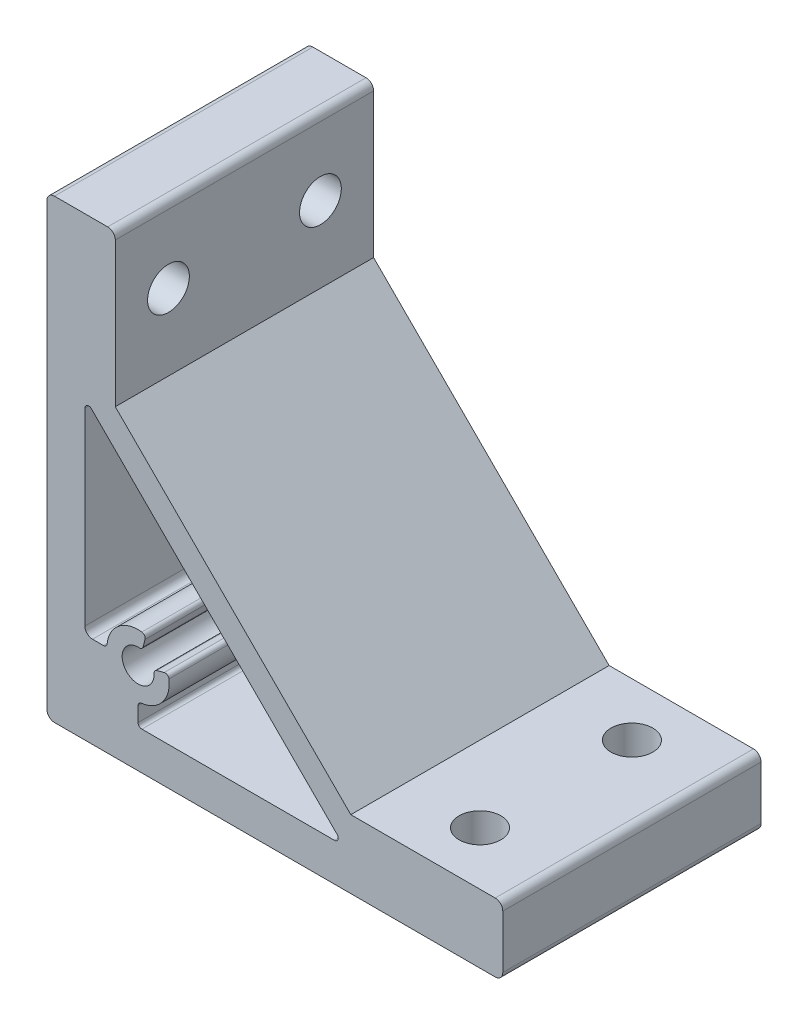
SolidWorks part; units mm, degrees
ref_plane "前视基准面" through (0, 0, 0) normal (0, 0, 1) x (1, 0, 0)
ref_plane "上视基准面" through (0, 0, 0) normal (0, 1, 0) x (1, 0, 0)
ref_plane "右视基准面" through (0, 0, 0) normal (1, 0, 0) x (0, 0, -1)
sketch "草图1" [suppressed] plane through (0, 0, 0) normal (0, 0, 1) x (1, 0, 0)
  line L12 (3, 3) -> (3, 19)
  line L13 (2, 20) -> (1, 20)
  line L14 (0, 19) -> (0, 1)
  line L15 (1, 0) -> (19, 0)
  line L16 (20, 1) -> (20, 2)
  line L17 (19, 3) -> (3, 3)
  arc A10 (3, 19) -> (2, 20) centre (2, 19) ccw
  arc A11 (1, 20) -> (0, 19) centre (1, 19) ccw
  arc A12 (0, 1) -> (1, 0) centre (1, 1) ccw
  arc A13 (19, 0) -> (20, 1) centre (19, 1) ccw
  arc A14 (20, 2) -> (19, 3) centre (19, 2) ccw
extrude "凸台-拉伸1" [suppressed] add sketch "草图1" against normal blind 14
sketch "草图2" [suppressed] plane through (0, 3, 0) normal (0, 1, 0) x (1, 0, 0)
  line L0 (19, 14) -> (3, 14) construction
  line L1 (0, 14) -> (0, 0) construction
  circle A0 centre (14, 7) radius 2.75
  dimension "D1" = 5.5
  dimension "D2" = 7
  dimension "D3" = 14
extrude "切除-拉伸1" [suppressed] cut sketch "草图2" against normal through all
sketch "草图3" [suppressed] plane through (3, 0, 0) normal (1, 0, 0) x (0, 0, -1)
  line L0 (0, 3) -> (0, 19) construction
  line L1 (14, 0) -> (0, 0) construction
  circle A0 centre (7, 14) radius 2.75
  dimension "D1" = 7
  dimension "D2" = 5.5
  dimension "D3" = 14
extrude "切除-拉伸2" [suppressed] cut sketch "草图3" against normal through all
sketch "草图4" [suppressed] plane through (0, 0, 0) normal (0, 0, 1) x (1, 0, 0)
  line L12 (3, 3) -> (3, 19)
  line L13 (2, 20) -> (1, 20)
  line L14 (0, 19) -> (0, 1)
  line L15 (1, 0) -> (19, 0)
  line L16 (20, 1) -> (20, 2)
  line L17 (19, 3) -> (3, 3)
  arc A10 (3, 19) -> (2, 20) centre (2, 19) ccw
  arc A11 (1, 20) -> (0, 19) centre (1, 19) ccw
  arc A12 (0, 1) -> (1, 0) centre (1, 1) ccw
  arc A13 (19, 0) -> (20, 1) centre (19, 1) ccw
  arc A14 (20, 2) -> (19, 3) centre (19, 2) ccw
extrude "凸台-拉伸2" [suppressed] add sketch "草图4" against normal blind 34
sketch "草图5" [suppressed] plane through (0, 3, 0) normal (0, 1, 0) x (1, 0, 0)
  line L0 (20, 17) -> (-10.7961, 17) construction
  line L1 (20, 34) -> (20, 0) construction
  line L2 (0, 34) -> (0, 0) construction
  circle A0 centre (14, 27) radius 2.75
  circle A1 centre (14, 7) radius 2.75
  dimension "D1" = 5.5
  dimension "D2" = 20
  dimension "D3" = 14
extrude "切除-拉伸3" [suppressed] cut sketch "草图5" against normal through all
sketch "草图6" [suppressed] plane through (3, 0, 0) normal (1, 0, 0) x (0, 0, -1)
  line L0 (17, 20) -> (17, -1.671) construction
  line L1 (34, 20) -> (0, 20) construction
  line L2 (34, 0) -> (0, 0) construction
  circle A0 centre (7, 14) radius 2.75
  circle A1 centre (27, 14) radius 2.75
  dimension "D1" = 5.5
  dimension "D2" = 20
  dimension "D3" = 14
extrude "切除-拉伸4" [suppressed] cut sketch "草图6" against normal through all
sketch "草图7" [suppressed] plane through (0, 0, 0) normal (0, 0, 1) x (1, 0, 0)
  line L12 (3, 3) -> (3, 19)
  line L13 (2, 20) -> (1, 20)
  line L14 (0, 19) -> (0, 1)
  line L15 (1, 0) -> (19, 0)
  line L16 (20, 1) -> (20, 2)
  line L17 (19, 3) -> (3, 3)
  arc A10 (3, 19) -> (2, 20) centre (2, 19) ccw
  arc A11 (1, 20) -> (0, 19) centre (1, 19) ccw
  arc A12 (0, 1) -> (1, 0) centre (1, 1) ccw
  arc A13 (19, 0) -> (20, 1) centre (19, 1) ccw
  arc A14 (20, 2) -> (19, 3) centre (19, 2) ccw
extrude "凸台-拉伸3" [suppressed] add sketch "草图7" against normal blind 54
sketch "草图8" [suppressed] plane through (0, 3, 0) normal (0, 1, 0) x (1, 0, 0)
  line L0 (20, 27) -> (-6.5003, 27) construction
  line L1 (20, 54) -> (20, 0) construction
  line L2 (0, 54) -> (0, 0) construction
  circle A0 centre (14, 47) radius 2.75
  circle A1 centre (14, 27) radius 2.75
  circle A2 centre (14, 7) radius 2.75
  dimension "D1" = 5.5
  dimension "D2" = 20
  dimension "D3" = 14
extrude "切除-拉伸5" [suppressed] cut sketch "草图8" against normal through all
sketch "草图9" [suppressed] plane through (3, 0, 0) normal (1, 0, 0) x (0, 0, -1)
  line L0 (27, 20) -> (27, 28.1098) construction
  line L1 (54, 20) -> (0, 20) construction
  line L2 (54, 0) -> (0, 0) construction
  circle A0 centre (7, 14) radius 2.75
  circle A1 centre (27, 14) radius 2.75
  circle A2 centre (47, 14) radius 2.75
  dimension "D1" = 5.5
  dimension "D2" = 20
  dimension "D3" = 14
extrude "切除-拉伸6" [suppressed] cut sketch "草图9" against normal through all
sketch "草图10" [suppressed] plane through (0, 0, 0) normal (0, 0, 1) x (1, 0, 0)
  line L20 (7.8119, 14.1881) -> (5, 17)
  line L21 (5, 17) -> (5, 34)
  line L22 (4, 35) -> (1, 35)
  line L23 (0, 34) -> (0, 1)
  line L24 (1, 0) -> (34, 0)
  line L25 (35, 1) -> (35, 4)
  line L26 (34, 5) -> (17, 5)
  line L27 (17, 5) -> (14.1881, 7.8119)
  line L28 (15.4436, 12.9222) -> (14.4646, 12.6602)
  line L29 (12.6602, 14.4646) -> (12.9222, 15.4436)
  arc A28 (5, 34) -> (4, 35) centre (4, 34) ccw
  arc A29 (1, 35) -> (0, 34) centre (1, 34) ccw
  arc A30 (0, 1) -> (1, 0) centre (1, 1) ccw
  arc A31 (34, 0) -> (35, 1) centre (34, 1) ccw
  arc A32 (35, 4) -> (34, 5) centre (34, 4) ccw
  arc A33 (14.265, 8.582) -> (14.1881, 7.8119) centre (14.5416, 8.1655) ccw
  arc A34 (14.265, 8.582) -> (16.069, 12.501) centre (11.9998, 11.9994) ccw
  arc A35 (16.069, 12.501) -> (15.4436, 12.9222) centre (15.5728, 12.4392) ccw
  arc A36 (14.4646, 12.6602) -> (14.095, 12.143) centre (14.5938, 12.1772) ccw
  arc A37 (12.143, 14.095) -> (14.095, 12.143) centre (11.9999, 11.9999) ccw
  arc A38 (12.143, 14.095) -> (12.6602, 14.4646) centre (12.1772, 14.5938) ccw
  arc A39 (12.9222, 15.4436) -> (12.501, 16.069) centre (12.4392, 15.5728) ccw
  arc A40 (12.501, 16.069) -> (8.582, 14.265) centre (11.9994, 11.9998) ccw
  arc A41 (7.8119, 14.1881) -> (8.582, 14.265) centre (8.1655, 14.5416) ccw
extrude "凸台-拉伸4" [suppressed] add sketch "草图10" against normal blind 14
sketch "草图11" [suppressed] plane through (0, 5, 0) normal (0, 1, 0) x (1, 0, 0)
  line L0 (34, 14) -> (17, 14) construction
  line L1 (0, 14) -> (0, 0) construction
  circle A0 centre (26, 7) radius 2.75
  dimension "D1" = 7
  dimension "D2" = 5.5
  dimension "D3" = 26
extrude "切除-拉伸7" [suppressed] cut sketch "草图11" against normal through all
sketch "草图12" [suppressed] plane through (5, 0, 0) normal (1, 0, 0) x (0, 0, -1)
  line L0 (0, 17) -> (0, 34) construction
  line L1 (14, 0) -> (0, 0) construction
  circle A0 centre (7, 26) radius 2.75
  dimension "D1" = 5.5
  dimension "D2" = 7
  dimension "D3" = 26
extrude "切除-拉伸8" [suppressed] cut sketch "草图12" against normal through all
sketch "草图13" [suppressed] plane through (0, 0, 0) normal (0, 0, 1) x (1, 0, 0)
  line L20 (7.8119, 14.1881) -> (5, 17)
  line L21 (5, 17) -> (5, 34)
  line L22 (4, 35) -> (1, 35)
  line L23 (0, 34) -> (0, 1)
  line L24 (1, 0) -> (34, 0)
  line L25 (35, 1) -> (35, 4)
  line L26 (34, 5) -> (17, 5)
  line L27 (17, 5) -> (14.1881, 7.8119)
  line L28 (15.4436, 12.9222) -> (14.4646, 12.6602)
  line L29 (12.6602, 14.4646) -> (12.9222, 15.4436)
  arc A28 (5, 34) -> (4, 35) centre (4, 34) ccw
  arc A29 (1, 35) -> (0, 34) centre (1, 34) ccw
  arc A30 (0, 1) -> (1, 0) centre (1, 1) ccw
  arc A31 (34, 0) -> (35, 1) centre (34, 1) ccw
  arc A32 (35, 4) -> (34, 5) centre (34, 4) ccw
  arc A33 (14.265, 8.582) -> (14.1881, 7.8119) centre (14.5416, 8.1655) ccw
  arc A34 (14.265, 8.582) -> (16.069, 12.501) centre (11.9998, 11.9994) ccw
  arc A35 (16.069, 12.501) -> (15.4436, 12.9222) centre (15.5728, 12.4392) ccw
  arc A36 (14.4646, 12.6602) -> (14.095, 12.143) centre (14.5938, 12.1772) ccw
  arc A37 (12.143, 14.095) -> (14.095, 12.143) centre (11.9999, 11.9999) ccw
  arc A38 (12.143, 14.095) -> (12.6602, 14.4646) centre (12.1772, 14.5938) ccw
  arc A39 (12.9222, 15.4436) -> (12.501, 16.069) centre (12.4392, 15.5728) ccw
  arc A40 (12.501, 16.069) -> (8.582, 14.265) centre (11.9994, 11.9998) ccw
  arc A41 (7.8119, 14.1881) -> (8.582, 14.265) centre (8.1655, 14.5416) ccw
extrude "凸台-拉伸5" [suppressed] add sketch "草图13" against normal blind 34
sketch "草图14" [suppressed] plane through (0, 5, 0) normal (0, 1, 0) x (1, 0, 0)
  line L0 (35, 17) -> (-9.0369, 17) construction
  line L1 (35, 34) -> (35, 0) construction
  line L2 (0, 34) -> (0, 0) construction
  circle A0 centre (26, 27) radius 2.75
  circle A1 centre (26, 7) radius 2.75
  dimension "D1" = 5.5
  dimension "D2" = 20
  dimension "D3" = 26
extrude "切除-拉伸9" [suppressed] cut sketch "草图14" against normal through all
sketch "草图15" [suppressed] plane through (5, 0, 0) normal (1, 0, 0) x (0, 0, -1)
  line L0 (17, 35) -> (17, -2.0911) construction
  line L1 (34, 35) -> (0, 35) construction
  line L2 (34, 0) -> (0, 0) construction
  circle A0 centre (7, 26) radius 2.75
  circle A1 centre (27, 26) radius 2.75
  dimension "D1" = 5.5
  dimension "D2" = 20
  dimension "D3" = 26
extrude "切除-拉伸10" [suppressed] cut sketch "草图15" against normal through all
sketch "草图16" [suppressed] plane through (0, 0, 0) normal (0, 0, 1) x (1, 0, 0)
  line L20 (7.8119, 14.1881) -> (5, 17)
  line L21 (5, 17) -> (5, 34)
  line L22 (4, 35) -> (1, 35)
  line L23 (0, 34) -> (0, 1)
  line L24 (1, 0) -> (34, 0)
  line L25 (35, 1) -> (35, 4)
  line L26 (34, 5) -> (17, 5)
  line L27 (17, 5) -> (14.1881, 7.8119)
  line L28 (15.4436, 12.9222) -> (14.4646, 12.6602)
  line L29 (12.6602, 14.4646) -> (12.9222, 15.4436)
  arc A28 (5, 34) -> (4, 35) centre (4, 34) ccw
  arc A29 (1, 35) -> (0, 34) centre (1, 34) ccw
  arc A30 (0, 1) -> (1, 0) centre (1, 1) ccw
  arc A31 (34, 0) -> (35, 1) centre (34, 1) ccw
  arc A32 (35, 4) -> (34, 5) centre (34, 4) ccw
  arc A33 (14.265, 8.582) -> (14.1881, 7.8119) centre (14.5416, 8.1655) ccw
  arc A34 (14.265, 8.582) -> (16.069, 12.501) centre (11.9998, 11.9994) ccw
  arc A35 (16.069, 12.501) -> (15.4436, 12.9222) centre (15.5728, 12.4392) ccw
  arc A36 (14.4646, 12.6602) -> (14.095, 12.143) centre (14.5938, 12.1772) ccw
  arc A37 (12.143, 14.095) -> (14.095, 12.143) centre (11.9999, 11.9999) ccw
  arc A38 (12.143, 14.095) -> (12.6602, 14.4646) centre (12.1772, 14.5938) ccw
  arc A39 (12.9222, 15.4436) -> (12.501, 16.069) centre (12.4392, 15.5728) ccw
  arc A40 (12.501, 16.069) -> (8.582, 14.265) centre (11.9994, 11.9998) ccw
  arc A41 (7.8119, 14.1881) -> (8.582, 14.265) centre (8.1655, 14.5416) ccw
extrude "凸台-拉伸6" [suppressed] add sketch "草图16" against normal blind 54
sketch "草图17" [suppressed] plane through (0, 5, 0) normal (0, 1, 0) x (1, 0, 0)
  line L0 (35, 27) -> (46.9961, 27) construction
  line L1 (35, 54) -> (35, 0) construction
  line L2 (0, 54) -> (0, 0) construction
  circle A0 centre (26, 47) radius 2.75
  circle A1 centre (26, 27) radius 2.75
  circle A2 centre (26, 7) radius 2.75
  dimension "D1" = 5.5
  dimension "D2" = 20
  dimension "D3" = 26
extrude "切除-拉伸11" [suppressed] cut sketch "草图17" against normal through all
sketch "草图18" [suppressed] plane through (5, 0, 0) normal (1, 0, 0) x (0, 0, -1)
  line L0 (27, 35) -> (27, 41.3305) construction
  line L1 (54, 35) -> (0, 35) construction
  line L2 (54, 0) -> (0, 0) construction
  circle A0 centre (7, 26) radius 2.75
  circle A1 centre (27, 26) radius 2.75
  circle A2 centre (47, 26) radius 2.75
  dimension "D1" = 5.5
  dimension "D2" = 20
  dimension "D3" = 26
extrude "切除-拉伸12" [suppressed] cut sketch "草图18" against normal through all
sketch "草图19" [suppressed] plane through (0, 0, 0) normal (0, 0, 1) x (1, 0, 0)
  line L16 (-14.794, 9) -> (-54, 9)
  line L17 (-55, 8) -> (-55, 1)
  line L18 (-54, 0) -> (-1, 0)
  line L19 (0, 1) -> (0, 54)
  line L20 (-1, 55) -> (-8, 55)
  line L21 (-9, 54) -> (-9, 14.795)
  line L22 (-12.9219, 15.4435) -> (-12.6599, 14.4646)
  line L23 (-14.4641, 12.66) -> (-15.443, 12.923)
  arc A24 (-15.443, 12.923) -> (-16.069, 12.501) centre (-15.5727, 12.4401) ccw
  arc A25 (-16.069, 12.501) -> (-14.794, 9) centre (-11.9997, 12.0003) ccw
  arc A26 (-54, 9) -> (-55, 8) centre (-54, 8) ccw
  arc A27 (-55, 1) -> (-54, 0) centre (-54, 1) ccw
  arc A28 (-1, 0) -> (0, 1) centre (-1, 1) ccw
  arc A29 (0, 54) -> (-1, 55) centre (-1, 54) ccw
  arc A30 (-8, 55) -> (-9, 54) centre (-8, 54) ccw
  arc A31 (-9, 14.795) -> (-12.5, 16.069) centre (-11.9994, 11.9997) ccw
  arc A32 (-12.5, 16.069) -> (-12.9219, 15.4435) centre (-12.4389, 15.5728) ccw
  arc A33 (-12.6599, 14.4646) -> (-12.143, 14.095) centre (-12.1769, 14.5939) ccw
  arc A34 (-14.095, 12.143) -> (-12.143, 14.095) centre (-11.9999, 11.9999) ccw
  arc A35 (-14.095, 12.143) -> (-14.4641, 12.66) centre (-14.5938, 12.1772) ccw
extrude "凸台-拉伸7" [suppressed] add sketch "草图19" against normal blind 14
sketch "草图20" [suppressed] plane through (-9, 0, 0) normal (-1, 0, 0) x (0, 0, 1)
  line L0 (-14, 54) -> (-14, 14.795) construction
  line L1 (-14, 0) -> (0, 0) construction
  circle A0 centre (-7, 25) radius 2.75
  circle A1 centre (-7, 45) radius 2.75
  dimension "D1" = 5.5
  dimension "D2" = 7
  dimension "D3" = 25
  dimension "D4" = 45
extrude "切除-拉伸13" [suppressed] cut sketch "草图20" against normal through all
sketch "草图21" [suppressed] plane through (0, 9, 0) normal (0, 1, 0) x (1, 0, 0)
  line L0 (-14.794, 0) -> (-54, 0) construction
  line L1 (0, 14) -> (0, 0) construction
  circle A0 centre (-45, 7) radius 2.75
  circle A1 centre (-25, 7) radius 2.75
  dimension "D1" = 5.5
  dimension "D2" = 7
  dimension "D3" = 25
  dimension "D4" = 45
extrude "切除-拉伸14" [suppressed] cut sketch "草图21" against normal through all
sketch "草图22" [suppressed] plane through (0, 0, 0) normal (0, 0, 1) x (1, 0, 0)
  line L16 (-14.794, 9) -> (-54, 9)
  line L17 (-55, 8) -> (-55, 1)
  line L18 (-54, 0) -> (-1, 0)
  line L19 (0, 1) -> (0, 54)
  line L20 (-1, 55) -> (-8, 55)
  line L21 (-9, 54) -> (-9, 14.795)
  line L22 (-12.9219, 15.4435) -> (-12.6599, 14.4646)
  line L23 (-14.4641, 12.66) -> (-15.443, 12.923)
  arc A24 (-15.443, 12.923) -> (-16.069, 12.501) centre (-15.5727, 12.4401) ccw
  arc A25 (-16.069, 12.501) -> (-14.794, 9) centre (-11.9997, 12.0003) ccw
  arc A26 (-54, 9) -> (-55, 8) centre (-54, 8) ccw
  arc A27 (-55, 1) -> (-54, 0) centre (-54, 1) ccw
  arc A28 (-1, 0) -> (0, 1) centre (-1, 1) ccw
  arc A29 (0, 54) -> (-1, 55) centre (-1, 54) ccw
  arc A30 (-8, 55) -> (-9, 54) centre (-8, 54) ccw
  arc A31 (-9, 14.795) -> (-12.5, 16.069) centre (-11.9994, 11.9997) ccw
  arc A32 (-12.5, 16.069) -> (-12.9219, 15.4435) centre (-12.4389, 15.5728) ccw
  arc A33 (-12.6599, 14.4646) -> (-12.143, 14.095) centre (-12.1769, 14.5939) ccw
  arc A34 (-14.095, 12.143) -> (-12.143, 14.095) centre (-11.9999, 11.9999) ccw
  arc A35 (-14.095, 12.143) -> (-14.4641, 12.66) centre (-14.5938, 12.1772) ccw
extrude "凸台-拉伸8" [suppressed] add sketch "草图22" against normal blind 34
sketch "草图23" [suppressed] plane through (-9, 0, 0) normal (-1, 0, 0) x (0, 0, 1)
  line L0 (-17, 55) -> (-17, 18.2791) construction
  line L1 (-34, 55) -> (0, 55) construction
  line L2 (-34, 0) -> (0, 0) construction
  circle A0 centre (-27, 45) radius 2.75
  circle A1 centre (-7, 45) radius 2.75
  circle A2 centre (-27, 25) radius 2.75
  circle A3 centre (-7, 25) radius 2.75
  dimension "D1" = 5.5
  dimension "D2" = 20
  dimension "D3" = 25
  dimension "D4" = 45
extrude "切除-拉伸15" [suppressed] cut sketch "草图23" against normal through all
sketch "草图24" [suppressed] plane through (0, 9, 0) normal (0, 1, 0) x (1, 0, 0)
  line L0 (-55, 17) -> (-20.4322, 17) construction
  line L1 (-55, 34) -> (-55, 0) construction
  line L2 (0, 34) -> (0, 0) construction
  circle A0 centre (-45, 27) radius 2.75
  circle A1 centre (-25, 27) radius 2.75
  circle A2 centre (-45, 7) radius 2.75
  circle A3 centre (-25, 7) radius 2.75
  dimension "D1" = 5.5
  dimension "D2" = 20
  dimension "D3" = 25
  dimension "D4" = 45
extrude "切除-拉伸16" [suppressed] cut sketch "草图24" against normal through all
sketch "草图25" [suppressed] plane through (0, 0, 0) normal (0, 0, 1) x (1, 0, 0)
  line L16 (-14.794, 9) -> (-54, 9)
  line L17 (-55, 8) -> (-55, 1)
  line L18 (-54, 0) -> (-1, 0)
  line L19 (0, 1) -> (0, 54)
  line L20 (-1, 55) -> (-8, 55)
  line L21 (-9, 54) -> (-9, 14.795)
  line L22 (-12.9219, 15.4435) -> (-12.6599, 14.4646)
  line L23 (-14.4641, 12.66) -> (-15.443, 12.923)
  arc A24 (-15.443, 12.923) -> (-16.069, 12.501) centre (-15.5727, 12.4401) ccw
  arc A25 (-16.069, 12.501) -> (-14.794, 9) centre (-11.9997, 12.0003) ccw
  arc A26 (-54, 9) -> (-55, 8) centre (-54, 8) ccw
  arc A27 (-55, 1) -> (-54, 0) centre (-54, 1) ccw
  arc A28 (-1, 0) -> (0, 1) centre (-1, 1) ccw
  arc A29 (0, 54) -> (-1, 55) centre (-1, 54) ccw
  arc A30 (-8, 55) -> (-9, 54) centre (-8, 54) ccw
  arc A31 (-9, 14.795) -> (-12.5, 16.069) centre (-11.9994, 11.9997) ccw
  arc A32 (-12.5, 16.069) -> (-12.9219, 15.4435) centre (-12.4389, 15.5728) ccw
  arc A33 (-12.6599, 14.4646) -> (-12.143, 14.095) centre (-12.1769, 14.5939) ccw
  arc A34 (-14.095, 12.143) -> (-12.143, 14.095) centre (-11.9999, 11.9999) ccw
  arc A35 (-14.095, 12.143) -> (-14.4641, 12.66) centre (-14.5938, 12.1772) ccw
extrude "凸台-拉伸9" [suppressed] add sketch "草图25" against normal blind 54
sketch "草图26" [suppressed] plane through (-9, 0, 0) normal (-1, 0, 0) x (0, 0, 1)
  line L0 (-27, 55) -> (-27, 17.8329) construction
  line L1 (-54, 55) -> (0, 55) construction
  line L2 (-54, 0) -> (0, 0) construction
  circle A0 centre (-47, 45) radius 2.75
  circle A1 centre (-27, 45) radius 2.75
  circle A2 centre (-7, 45) radius 2.75
  circle A3 centre (-7, 25) radius 2.75
  circle A4 centre (-27, 25) radius 2.75
  circle A5 centre (-47, 25) radius 2.75
  dimension "D1" = 5.5
  dimension "D2" = 20
  dimension "D3" = 25
  dimension "D4" = 45
extrude "切除-拉伸17" [suppressed] cut sketch "草图26" against normal through all
sketch "草图27" [suppressed] plane through (0, 9, 0) normal (0, 1, 0) x (1, 0, 0)
  line L0 (-55, 27) -> (-66.2684, 27) construction
  line L1 (-55, 54) -> (-55, 0) construction
  line L2 (0, 54) -> (0, 0) construction
  circle A0 centre (-45, 47) radius 2.75
  circle A1 centre (-25, 47) radius 2.75
  circle A2 centre (-45, 27) radius 2.75
  circle A3 centre (-25, 27) radius 2.75
  circle A4 centre (-45, 7) radius 2.75
  circle A5 centre (-25, 7) radius 2.75
  dimension "D1" = 5.5
  dimension "D2" = 20
  dimension "D3" = 25
  dimension "D4" = 45
extrude "切除-拉伸18" [suppressed] cut sketch "草图27" against normal through all
sketch "草图28" [suppressed] plane through (0, 0, 0) normal (0, 0, 1) x (1, 0, 0)
  line L14 (9, 30) -> (9, 49)
  line L15 (8, 50) -> (1, 50)
  line L16 (0, 49) -> (0, 1)
  line L17 (1, 0) -> (49, 0)
  line L18 (50, 1) -> (50, 8)
  line L19 (49, 9) -> (30, 9)
  line L20 (30, 9) -> (9, 30)
  line L28 (5.5, 12) -> (7.428, 12)
  line L29 (5, 27.8439) -> (5, 12.5)
  line L30 (28.1965, 5.8535) -> (5.8536, 28.1974)
  line L31 (12.5, 5) -> (27.8429, 5)
  line L32 (12, 7.4269) -> (12, 5.5)
  line L33 (14.4641, 12.6598) -> (15.444, 12.923)
  line L34 (12.9231, 15.4435) -> (12.6612, 14.4646)
  arc A10 (9, 49) -> (8, 50) centre (8, 49) ccw
  arc A11 (1, 50) -> (0, 49) centre (1, 49) ccw
  arc A12 (0, 1) -> (1, 0) centre (1, 1) ccw
  arc A13 (49, 0) -> (50, 1) centre (49, 1) ccw
  arc A14 (50, 8) -> (49, 9) centre (49, 8) ccw
  arc A36 (7.428, 12) -> (7.925, 12.445) centre (7.428, 12.5) ccw
  arc A37 (5, 12.5) -> (5.5, 12) centre (5.5, 12.5) ccw
  arc A38 (5.8536, 28.1974) -> (5, 27.8439) centre (5.5, 27.8439) ccw
  arc A39 (27.8429, 5) -> (28.1965, 5.8535) centre (27.8429, 5.5) ccw
  arc A40 (12, 5.5) -> (12.5, 5) centre (12.5, 5.5) ccw
  arc A41 (12.446, 7.924) -> (12, 7.4269) centre (12.5, 7.4269) ccw
  arc A42 (12.446, 7.924) -> (16.07, 12.501) centre (12.0008, 11.9998) ccw
  arc A43 (16.07, 12.501) -> (15.444, 12.923) centre (15.5737, 12.4401) ccw
  arc A44 (14.4641, 12.6598) -> (14.095, 12.143) centre (14.5939, 12.1769) ccw
  arc A45 (12.144, 14.095) -> (14.095, 12.143) centre (11.9999, 12) ccw
  arc A46 (12.144, 14.095) -> (12.6612, 14.4646) centre (12.1782, 14.5938) ccw
  arc A47 (12.9231, 15.4435) -> (12.501, 16.069) centre (12.4401, 15.5727) ccw
  arc A48 (12.501, 16.069) -> (7.925, 12.445) centre (12.0007, 11.9996) ccw
extrude "凸台-拉伸10" [suppressed] add sketch "草图28" along normal blind 14
sketch "草图29" [suppressed] plane through (9, 0, 0) normal (1, 0, 0) x (0, 0, -1)
  line L0 (-14, 30) -> (-14, 49) construction
  line L1 (-14, 0) -> (0, 0) construction
  circle A0 centre (-7, 40) radius 2.75
  dimension "D1" = 7
  dimension "D2" = 5.5
  dimension "D3" = 40
extrude "切除-拉伸19" [suppressed] cut sketch "草图29" against normal through all
sketch "草图30" [suppressed] plane through (0, 9, 0) normal (0, 1, 0) x (1, 0, 0)
  line L0 (49, 0) -> (30, 0) construction
  line L1 (0, -14) -> (0, 0) construction
  circle A0 centre (40, -7) radius 2.75
  dimension "D1" = 5.5
  dimension "D2" = 7
  dimension "D3" = 40
extrude "切除-拉伸20" [suppressed] cut sketch "草图30" against normal through all
sketch "草图31" [suppressed] plane through (0, 0, 0) normal (0, 0, 1) x (1, 0, 0)
  line L14 (9, 30) -> (9, 49)
  line L15 (8, 50) -> (1, 50)
  line L16 (0, 49) -> (0, 1)
  line L17 (1, 0) -> (49, 0)
  line L18 (50, 1) -> (50, 8)
  line L19 (49, 9) -> (30, 9)
  line L20 (30, 9) -> (9, 30)
  line L28 (5.5, 12) -> (7.428, 12)
  line L29 (5, 27.8439) -> (5, 12.5)
  line L30 (28.1965, 5.8535) -> (5.8536, 28.1974)
  line L31 (12.5, 5) -> (27.8429, 5)
  line L32 (12, 7.4269) -> (12, 5.5)
  line L33 (14.4641, 12.6598) -> (15.444, 12.923)
  line L34 (12.9231, 15.4435) -> (12.6612, 14.4646)
  arc A10 (9, 49) -> (8, 50) centre (8, 49) ccw
  arc A11 (1, 50) -> (0, 49) centre (1, 49) ccw
  arc A12 (0, 1) -> (1, 0) centre (1, 1) ccw
  arc A13 (49, 0) -> (50, 1) centre (49, 1) ccw
  arc A14 (50, 8) -> (49, 9) centre (49, 8) ccw
  arc A36 (7.428, 12) -> (7.925, 12.445) centre (7.428, 12.5) ccw
  arc A37 (5, 12.5) -> (5.5, 12) centre (5.5, 12.5) ccw
  arc A38 (5.8536, 28.1974) -> (5, 27.8439) centre (5.5, 27.8439) ccw
  arc A39 (27.8429, 5) -> (28.1965, 5.8535) centre (27.8429, 5.5) ccw
  arc A40 (12, 5.5) -> (12.5, 5) centre (12.5, 5.5) ccw
  arc A41 (12.446, 7.924) -> (12, 7.4269) centre (12.5, 7.4269) ccw
  arc A42 (12.446, 7.924) -> (16.07, 12.501) centre (12.0008, 11.9998) ccw
  arc A43 (16.07, 12.501) -> (15.444, 12.923) centre (15.5737, 12.4401) ccw
  arc A44 (14.4641, 12.6598) -> (14.095, 12.143) centre (14.5939, 12.1769) ccw
  arc A45 (12.144, 14.095) -> (14.095, 12.143) centre (11.9999, 12) ccw
  arc A46 (12.144, 14.095) -> (12.6612, 14.4646) centre (12.1782, 14.5938) ccw
  arc A47 (12.9231, 15.4435) -> (12.501, 16.069) centre (12.4401, 15.5727) ccw
  arc A48 (12.501, 16.069) -> (7.925, 12.445) centre (12.0007, 11.9996) ccw
extrude "凸台-拉伸11" [suppressed] add sketch "草图31" against normal blind 34
sketch "草图32" [suppressed] plane through (0, 9, 0) normal (0, 1, 0) x (1, 0, 0)
  line L0 (50, 17) -> (60.62, 17) construction
  line L1 (50, 34) -> (50, 0) construction
  line L2 (0, 34) -> (0, 0) construction
  circle A0 centre (40, 27) radius 2.75
  circle A1 centre (40, 7) radius 2.75
  dimension "D1" = 5.5
  dimension "D2" = 20
  dimension "D3" = 40
extrude "切除-拉伸21" [suppressed] cut sketch "草图32" against normal through all
sketch "草图33" [suppressed] plane through (9, 0, 0) normal (1, 0, 0) x (0, 0, -1)
  line L0 (17, 50) -> (17, 18.713) construction
  line L1 (34, 50) -> (0, 50) construction
  line L2 (34, 0) -> (0, 0) construction
  circle A0 centre (7, 40) radius 2.75
  circle A1 centre (27, 40) radius 2.75
  dimension "D1" = 5.5
  dimension "D2" = 20
  dimension "D3" = 40
extrude "切除-拉伸22" [suppressed] cut sketch "草图33" against normal through all
sketch "草图34" [suppressed] plane through (0, 0, 0) normal (0, 0, 1) x (1, 0, 0)
  line L14 (9, 30) -> (9, 49)
  line L15 (8, 50) -> (1, 50)
  line L16 (0, 49) -> (0, 1)
  line L17 (1, 0) -> (49, 0)
  line L18 (50, 1) -> (50, 8)
  line L19 (49, 9) -> (30, 9)
  line L20 (30, 9) -> (9, 30)
  line L28 (5.5, 12) -> (7.428, 12)
  line L29 (5, 27.8439) -> (5, 12.5)
  line L30 (28.1965, 5.8535) -> (5.8536, 28.1974)
  line L31 (12.5, 5) -> (27.8429, 5)
  line L32 (12, 7.4269) -> (12, 5.5)
  line L33 (14.4641, 12.6598) -> (15.444, 12.923)
  line L34 (12.9231, 15.4435) -> (12.6612, 14.4646)
  arc A10 (9, 49) -> (8, 50) centre (8, 49) ccw
  arc A11 (1, 50) -> (0, 49) centre (1, 49) ccw
  arc A12 (0, 1) -> (1, 0) centre (1, 1) ccw
  arc A13 (49, 0) -> (50, 1) centre (49, 1) ccw
  arc A14 (50, 8) -> (49, 9) centre (49, 8) ccw
  arc A36 (7.428, 12) -> (7.925, 12.445) centre (7.428, 12.5) ccw
  arc A37 (5, 12.5) -> (5.5, 12) centre (5.5, 12.5) ccw
  arc A38 (5.8536, 28.1974) -> (5, 27.8439) centre (5.5, 27.8439) ccw
  arc A39 (27.8429, 5) -> (28.1965, 5.8535) centre (27.8429, 5.5) ccw
  arc A40 (12, 5.5) -> (12.5, 5) centre (12.5, 5.5) ccw
  arc A41 (12.446, 7.924) -> (12, 7.4269) centre (12.5, 7.4269) ccw
  arc A42 (12.446, 7.924) -> (16.07, 12.501) centre (12.0008, 11.9998) ccw
  arc A43 (16.07, 12.501) -> (15.444, 12.923) centre (15.5737, 12.4401) ccw
  arc A44 (14.4641, 12.6598) -> (14.095, 12.143) centre (14.5939, 12.1769) ccw
  arc A45 (12.144, 14.095) -> (14.095, 12.143) centre (11.9999, 12) ccw
  arc A46 (12.144, 14.095) -> (12.6612, 14.4646) centre (12.1782, 14.5938) ccw
  arc A47 (12.9231, 15.4435) -> (12.501, 16.069) centre (12.4401, 15.5727) ccw
  arc A48 (12.501, 16.069) -> (7.925, 12.445) centre (12.0007, 11.9996) ccw
extrude "凸台-拉伸12" [suppressed] add sketch "草图34" against normal blind 54
sketch "草图35" [suppressed] plane through (0, 9, 0) normal (0, 1, 0) x (1, 0, 0)
  line L0 (50, 27) -> (60.775, 27) construction
  line L1 (50, 54) -> (50, 0) construction
  line L2 (0, 54) -> (0, 0) construction
  circle A0 centre (40, 47) radius 2.75
  circle A1 centre (40, 27) radius 2.75
  circle A2 centre (40, 7) radius 2.75
  dimension "D1" = 5.5
  dimension "D2" = 20
  dimension "D3" = 40
extrude "切除-拉伸23" [suppressed] cut sketch "草图35" against normal through all
sketch "草图36" [suppressed] plane through (9, 0, 0) normal (1, 0, 0) x (0, 0, -1)
  line L0 (27, 50) -> (27, 56.3689) construction
  line L1 (54, 50) -> (0, 50) construction
  line L2 (54, 0) -> (0, 0) construction
  circle A0 centre (7, 40) radius 2.75
  circle A1 centre (27, 40) radius 2.75
  circle A2 centre (47, 40) radius 2.75
  dimension "D1" = 5.5
  dimension "D2" = 20
  dimension "D3" = 40
extrude "切除-拉伸24" [suppressed] cut sketch "草图36" against normal through all
sketch "草图37" [suppressed] plane through (0, 0, 0) normal (0, 0, 1) x (1, 0, 0)
  line L14 (40, 9) -> (9, 40)
  line L15 (9, 40) -> (9, 59)
  line L16 (8, 60) -> (1, 60)
  line L17 (0, 59) -> (0, 1)
  line L18 (1, 0) -> (59, 0)
  line L19 (60, 1) -> (60, 8)
  line L20 (59, 9) -> (40, 9)
  line L28 (6, 12) -> (7.428, 12)
  line L29 (5, 37.8429) -> (5, 13)
  line L30 (38.1964, 5.8536) -> (5.8536, 38.1964)
  line L31 (12.5, 5) -> (37.844, 5)
  line L32 (12, 7.4269) -> (12, 5.5)
  line L33 (14.4656, 12.6602) -> (15.4446, 12.9222)
  line L34 (12.9231, 15.4435) -> (12.6612, 14.4646)
  arc A10 (9, 59) -> (8, 60) centre (8, 59) ccw
  arc A11 (1, 60) -> (0, 59) centre (1, 59) ccw
  arc A12 (0, 1) -> (1, 0) centre (1, 1) ccw
  arc A13 (59, 0) -> (60, 1) centre (59, 1) ccw
  arc A14 (60, 8) -> (59, 9) centre (59, 8) ccw
  arc A36 (12.501, 16.069) -> (7.925, 12.445) centre (12.0007, 11.9996) ccw
  arc A37 (7.428, 12) -> (7.925, 12.445) centre (7.428, 12.5) ccw
  arc A38 (5, 13) -> (6, 12) centre (6, 13) ccw
  arc A39 (5.8536, 38.1964) -> (5, 37.8429) centre (5.5, 37.8429) ccw
  arc A40 (37.844, 5) -> (38.1964, 5.8536) centre (37.8429, 5.5) ccw
  arc A41 (12, 5.5) -> (12.5, 5) centre (12.5, 5.5) ccw
  arc A42 (12.446, 7.924) -> (12, 7.4269) centre (12.5, 7.4269) ccw
  arc A43 (12.446, 7.924) -> (16.07, 12.501) centre (12.0008, 11.9998) ccw
  arc A44 (16.07, 12.501) -> (15.4446, 12.9222) centre (15.5738, 12.4392) ccw
  arc A45 (14.4656, 12.6602) -> (14.096, 12.143) centre (14.5948, 12.1772) ccw
  arc A46 (12.144, 14.095) -> (14.096, 12.143) centre (12.0009, 11.9999) ccw
  arc A47 (12.144, 14.095) -> (12.6612, 14.4646) centre (12.1782, 14.5938) ccw
  arc A48 (12.9231, 15.4435) -> (12.501, 16.069) centre (12.4401, 15.5727) ccw
extrude "凸台-拉伸13" [suppressed] add sketch "草图37" against normal blind 14
sketch "草图38" [suppressed] plane through (0, 9, 0) normal (0, 1, 0) x (1, 0, 0)
  line L0 (59, 14) -> (40, 14) construction
  line L1 (0, 14) -> (0, 0) construction
  circle A0 centre (50, 7) radius 2.75
  dimension "D1" = 5.5
  dimension "D2" = 7
  dimension "D3" = 50
extrude "切除-拉伸25" [suppressed] cut sketch "草图38" against normal through all
sketch "草图39" [suppressed] plane through (9, 0, 0) normal (1, 0, 0) x (0, 0, -1)
  line L0 (0, 40) -> (0, 59) construction
  line L1 (14, 0) -> (0, 0) construction
  circle A0 centre (7, 50) radius 2.75
  dimension "D1" = 5.5
  dimension "D2" = 7
  dimension "D3" = 50
extrude "切除-拉伸26" [suppressed] cut sketch "草图39" against normal through all
sketch "草图40" plane through (0, 0, 0) normal (0, 0, 1) x (1, 0, 0)
  line L14 (40, 9) -> (9, 40)
  line L15 (9, 40) -> (9, 59)
  line L16 (8, 60) -> (1, 60)
  line L17 (0, 59) -> (0, 1)
  line L18 (1, 0) -> (59, 0)
  line L19 (60, 1) -> (60, 8)
  line L20 (59, 9) -> (40, 9)
  line L28 (6, 12) -> (7.428, 12)
  line L29 (5, 37.8429) -> (5, 13)
  line L30 (38.1964, 5.8536) -> (5.8536, 38.1964)
  line L31 (12.5, 5) -> (37.844, 5)
  line L32 (12, 7.4269) -> (12, 5.5)
  line L33 (14.4656, 12.6602) -> (15.4446, 12.9222)
  line L34 (12.9231, 15.4435) -> (12.6612, 14.4646)
  arc A10 (9, 59) -> (8, 60) centre (8, 59) ccw
  arc A11 (1, 60) -> (0, 59) centre (1, 59) ccw
  arc A12 (0, 1) -> (1, 0) centre (1, 1) ccw
  arc A13 (59, 0) -> (60, 1) centre (59, 1) ccw
  arc A14 (60, 8) -> (59, 9) centre (59, 8) ccw
  arc A36 (12.501, 16.069) -> (7.925, 12.445) centre (12.0007, 11.9996) ccw
  arc A37 (7.428, 12) -> (7.925, 12.445) centre (7.428, 12.5) ccw
  arc A38 (5, 13) -> (6, 12) centre (6, 13) ccw
  arc A39 (5.8536, 38.1964) -> (5, 37.8429) centre (5.5, 37.8429) ccw
  arc A40 (37.844, 5) -> (38.1964, 5.8536) centre (37.8429, 5.5) ccw
  arc A41 (12, 5.5) -> (12.5, 5) centre (12.5, 5.5) ccw
  arc A42 (12.446, 7.924) -> (12, 7.4269) centre (12.5, 7.4269) ccw
  arc A43 (12.446, 7.924) -> (16.07, 12.501) centre (12.0008, 11.9998) ccw
  arc A44 (16.07, 12.501) -> (15.4446, 12.9222) centre (15.5738, 12.4392) ccw
  arc A45 (14.4656, 12.6602) -> (14.096, 12.143) centre (14.5948, 12.1772) ccw
  arc A46 (12.144, 14.095) -> (14.096, 12.143) centre (12.0009, 11.9999) ccw
  arc A47 (12.144, 14.095) -> (12.6612, 14.4646) centre (12.1782, 14.5938) ccw
  arc A48 (12.9231, 15.4435) -> (12.501, 16.069) centre (12.4401, 15.5727) ccw
extrude "凸台-拉伸14" add sketch "草图40" against normal blind 34
sketch "草图41" plane through (0, 9, 0) normal (0, 1, 0) x (1, 0, 0)
  line L0 (60, 17) -> (42.7252, 17) construction
  line L1 (60, 34) -> (60, 0) construction
  line L2 (0, 34) -> (0, 0) construction
  circle A0 centre (50, 27) radius 2.75
  circle A1 centre (50, 7) radius 2.75
  dimension "D1" = 5.5
  dimension "D2" = 20
  dimension "D3" = 50
extrude "切除-拉伸27" cut sketch "草图41" against normal through all
sketch "草图42" plane through (9, 0, 0) normal (1, 0, 0) x (0, 0, -1)
  line L0 (17, 60) -> (17, 43.1418) construction
  line L1 (34, 60) -> (0, 60) construction
  line L2 (34, 0) -> (0, 0) construction
  circle A0 centre (7, 50) radius 2.75
  circle A1 centre (27, 50) radius 2.75
  dimension "D1" = 5.5
  dimension "D2" = 50
  dimension "D3" = 20
extrude "切除-拉伸28" cut sketch "草图42" against normal through all
sketch "草图43" [suppressed] plane through (0, 0, 0) normal (0, 0, 1) x (1, 0, 0)
  line L14 (40, 9) -> (9, 40)
  line L15 (9, 40) -> (9, 59)
  line L16 (8, 60) -> (1, 60)
  line L17 (0, 59) -> (0, 1)
  line L18 (1, 0) -> (59, 0)
  line L19 (60, 1) -> (60, 8)
  line L20 (59, 9) -> (40, 9)
  line L28 (6, 12) -> (7.428, 12)
  line L29 (5, 37.8429) -> (5, 13)
  line L30 (38.1964, 5.8536) -> (5.8536, 38.1964)
  line L31 (12.5, 5) -> (37.844, 5)
  line L32 (12, 7.4269) -> (12, 5.5)
  line L33 (14.4656, 12.6602) -> (15.4446, 12.9222)
  line L34 (12.9231, 15.4435) -> (12.6612, 14.4646)
  arc A10 (9, 59) -> (8, 60) centre (8, 59) ccw
  arc A11 (1, 60) -> (0, 59) centre (1, 59) ccw
  arc A12 (0, 1) -> (1, 0) centre (1, 1) ccw
  arc A13 (59, 0) -> (60, 1) centre (59, 1) ccw
  arc A14 (60, 8) -> (59, 9) centre (59, 8) ccw
  arc A36 (12.501, 16.069) -> (7.925, 12.445) centre (12.0007, 11.9996) ccw
  arc A37 (7.428, 12) -> (7.925, 12.445) centre (7.428, 12.5) ccw
  arc A38 (5, 13) -> (6, 12) centre (6, 13) ccw
  arc A39 (5.8536, 38.1964) -> (5, 37.8429) centre (5.5, 37.8429) ccw
  arc A40 (37.844, 5) -> (38.1964, 5.8536) centre (37.8429, 5.5) ccw
  arc A41 (12, 5.5) -> (12.5, 5) centre (12.5, 5.5) ccw
  arc A42 (12.446, 7.924) -> (12, 7.4269) centre (12.5, 7.4269) ccw
  arc A43 (12.446, 7.924) -> (16.07, 12.501) centre (12.0008, 11.9998) ccw
  arc A44 (16.07, 12.501) -> (15.4446, 12.9222) centre (15.5738, 12.4392) ccw
  arc A45 (14.4656, 12.6602) -> (14.096, 12.143) centre (14.5948, 12.1772) ccw
  arc A46 (12.144, 14.095) -> (14.096, 12.143) centre (12.0009, 11.9999) ccw
  arc A47 (12.144, 14.095) -> (12.6612, 14.4646) centre (12.1782, 14.5938) ccw
  arc A48 (12.9231, 15.4435) -> (12.501, 16.069) centre (12.4401, 15.5727) ccw
extrude "凸台-拉伸15" [suppressed] add sketch "草图43" against normal blind 54
sketch "草图44" [suppressed] plane through (0, 9, 0) normal (0, 1, 0) x (1, 0, 0)
  line L0 (60, 27) -> (67.8923, 27) construction
  line L1 (60, 54) -> (60, 0) construction
  line L2 (0, 54) -> (0, 0) construction
  circle A0 centre (50, 47) radius 2.75
  circle A1 centre (50, 27) radius 2.75
  circle A2 centre (50, 7) radius 2.75
  dimension "D1" = 5.5
  dimension "D2" = 20
  dimension "D3" = 50
extrude "切除-拉伸29" [suppressed] cut sketch "草图44" against normal through all
sketch "草图45" [suppressed] plane through (9, 0, 0) normal (1, 0, 0) x (0, 0, -1)
  line L0 (27, 60) -> (27, 66.2617) construction
  line L1 (54, 60) -> (0, 60) construction
  line L2 (54, 0) -> (0, 0) construction
  circle A0 centre (7, 50) radius 2.75
  circle A1 centre (27, 50) radius 2.75
  circle A2 centre (47, 50) radius 2.75
  dimension "D1" = 5.5
  dimension "D2" = 20
  dimension "D3" = 50
extrude "切除-拉伸30" [suppressed] cut sketch "草图45" against normal through all
sketch "草图46" [suppressed] plane through (0, 0, 0) normal (0, 0, 1) x (1, 0, 0)
  line L14 (47.8087, 36.829) -> (61.2436, 50.2639)
  line L15 (61.2436, 51.6781) -> (56.2938, 56.6279)
  line L16 (54.8796, 56.6279) -> (0.4329, 2.1812)
  line L17 (1.8471, -1.233) -> (78.8467, -1.233)
  line L18 (79.8467, -0.233) -> (79.8467, 6.767)
  line L19 (78.8467, 7.767) -> (59.8467, 7.767)
  line L20 (59.8467, 7.767) -> (47.8087, 36.829)
  line L24 (20.3766, 7.061) -> (21.3809, 6.9291)
  line L25 (20.0167, 10.223) -> (19.4001, 9.4185)
  line L26 (41.2668, 35.9441) -> (18.3722, 13.0495)
  line L27 (55.5184, 5.1496) -> (42.8978, 35.6197)
  line L28 (22.2179, 3.767) -> (54.5945, 3.767)
  arc A10 (61.2436, 50.2639) -> (61.2436, 51.6781) centre (60.5365, 50.971) ccw
  arc A11 (56.2938, 56.6279) -> (54.8796, 56.6279) centre (55.5867, 55.9208) ccw
  arc A12 (0.4329, 2.1812) -> (1.8471, -1.233) centre (1.8471, 0.767) ccw
  arc A13 (78.8467, -1.233) -> (79.8467, -0.233) centre (78.8467, -0.233) ccw
  arc A14 (79.8467, 6.767) -> (78.8467, 7.767) centre (78.8467, 6.767) ccw
  arc A32 (21.3607, 5.282) -> (21.7977, 6.3) centre (17.8462, 7.3934) ccw
  arc A33 (21.7977, 6.3) -> (21.3809, 6.9291) centre (21.3158, 6.4333) ccw
  arc A34 (20.3766, 7.061) -> (19.8377, 6.725) centre (20.3115, 6.5652) ccw
  arc A35 (18.7807, 9.275) -> (19.8377, 6.725) centre (17.8471, 7.3939) ccw
  arc A36 (18.7807, 9.275) -> (19.4001, 9.4185) centre (19.0033, 9.7227) ccw
  arc A37 (20.0167, 10.223) -> (19.8667, 10.962) centre (19.6198, 10.5271) ccw
  arc A38 (19.8667, 10.962) -> (18.8377, 11.372) centre (17.8485, 7.3931) ccw
  arc A39 (18.3722, 13.0495) -> (18.8377, 11.372) centre (19.0793, 12.3423) ccw
  arc A40 (42.8978, 35.6197) -> (41.2668, 35.9441) centre (41.9739, 35.237) ccw
  arc A41 (54.5945, 3.767) -> (55.5184, 5.1496) centre (54.5945, 4.767) ccw
  arc A42 (21.3607, 5.282) -> (22.2179, 3.767) centre (22.2179, 4.767) ccw
extrude "凸台-拉伸16" [suppressed] add sketch "草图46" against normal blind 14
sketch "草图47" [suppressed] plane through (0, 7.767, 0) normal (0, 1, 0) x (1, 0, 0)
  line L0 (78.8467, 14) -> (59.8467, 14) construction
  line L1 (-0.1529, 14) -> (-0.1529, 0) construction
  circle A0 centre (69.8471, 7) radius 2.75
  dimension "D1" = 5.5
  dimension "D2" = 7
  dimension "D3" = 70
extrude "切除-拉伸31" [suppressed] cut sketch "草图47" against normal through all
sketch "草图48" [suppressed] plane through (5.4899, -5.4899, 0) normal (0.7071, -0.7071, 0) x (0, 0, -1)
  line L0 (0, 59.8478) -> (0, 78.8477) construction
  line L1 (0, -0.1516) -> (14, -0.1516) construction
  circle A0 centre (7, 69.8484) radius 2.75
  dimension "D1" = 5.5
  dimension "D2" = 7
  dimension "D3" = 70
extrude "切除-拉伸32" [suppressed] cut sketch "草图48" against normal through all
sketch "草图49" [suppressed] plane through (0, 0, 0) normal (0, 0, 1) x (1, 0, 0)
  line L14 (47.8087, 36.829) -> (61.2436, 50.2639)
  line L15 (61.2436, 51.6781) -> (56.2938, 56.6279)
  line L16 (54.8796, 56.6279) -> (0.4329, 2.1812)
  line L17 (1.8471, -1.233) -> (78.8467, -1.233)
  line L18 (79.8467, -0.233) -> (79.8467, 6.767)
  line L19 (78.8467, 7.767) -> (59.8467, 7.767)
  line L20 (59.8467, 7.767) -> (47.8087, 36.829)
  line L24 (20.3766, 7.061) -> (21.3809, 6.9291)
  line L25 (20.0167, 10.223) -> (19.4001, 9.4185)
  line L26 (41.2668, 35.9441) -> (18.3722, 13.0495)
  line L27 (55.5184, 5.1496) -> (42.8978, 35.6197)
  line L28 (22.2179, 3.767) -> (54.5945, 3.767)
  arc A10 (61.2436, 50.2639) -> (61.2436, 51.6781) centre (60.5365, 50.971) ccw
  arc A11 (56.2938, 56.6279) -> (54.8796, 56.6279) centre (55.5867, 55.9208) ccw
  arc A12 (0.4329, 2.1812) -> (1.8471, -1.233) centre (1.8471, 0.767) ccw
  arc A13 (78.8467, -1.233) -> (79.8467, -0.233) centre (78.8467, -0.233) ccw
  arc A14 (79.8467, 6.767) -> (78.8467, 7.767) centre (78.8467, 6.767) ccw
  arc A32 (21.3607, 5.282) -> (21.7977, 6.3) centre (17.8462, 7.3934) ccw
  arc A33 (21.7977, 6.3) -> (21.3809, 6.9291) centre (21.3158, 6.4333) ccw
  arc A34 (20.3766, 7.061) -> (19.8377, 6.725) centre (20.3115, 6.5652) ccw
  arc A35 (18.7807, 9.275) -> (19.8377, 6.725) centre (17.8471, 7.3939) ccw
  arc A36 (18.7807, 9.275) -> (19.4001, 9.4185) centre (19.0033, 9.7227) ccw
  arc A37 (20.0167, 10.223) -> (19.8667, 10.962) centre (19.6198, 10.5271) ccw
  arc A38 (19.8667, 10.962) -> (18.8377, 11.372) centre (17.8485, 7.3931) ccw
  arc A39 (18.3722, 13.0495) -> (18.8377, 11.372) centre (19.0793, 12.3423) ccw
  arc A40 (42.8978, 35.6197) -> (41.2668, 35.9441) centre (41.9739, 35.237) ccw
  arc A41 (54.5945, 3.767) -> (55.5184, 5.1496) centre (54.5945, 4.767) ccw
  arc A42 (21.3607, 5.282) -> (22.2179, 3.767) centre (22.2179, 4.767) ccw
extrude "凸台-拉伸17" [suppressed] add sketch "草图49" along normal blind 34
sketch "草图50" [suppressed] plane through (5.4899, -5.4899, 0) normal (0.7071, -0.7071, 0) x (0, 0, -1)
  line L0 (-17, 79.8477) -> (-17, 64.8771) construction
  line L1 (-34, 79.8477) -> (0, 79.8477) construction
  line L2 (-34, -0.1516) -> (0, -0.1516) construction
  circle A0 centre (-27, 69.8484) radius 2.75
  circle A1 centre (-7, 69.8484) radius 2.75
  dimension "D1" = 5.5
  dimension "D2" = 20
  dimension "D3" = 70
extrude "切除-拉伸33" [suppressed] cut sketch "草图50" against normal through all
sketch "草图51" [suppressed] plane through (0, 7.767, 0) normal (0, 1, 0) x (1, 0, 0)
  line L0 (79.8467, -17) -> (89.8279, -17) construction
  line L1 (79.8467, -34) -> (79.8467, 0) construction
  line L2 (-0.1529, 0) -> (-0.1529, -34) construction
  circle A0 centre (69.8471, -7) radius 2.75
  circle A1 centre (69.8471, -27) radius 2.75
  dimension "D1" = 5.5
  dimension "D2" = 20
  dimension "D3" = 70
extrude "切除-拉伸34" [suppressed] cut sketch "草图51" against normal through all
sketch "草图52" [suppressed] plane through (0, 0, 0) normal (0, 0, 1) x (1, 0, 0)
  line L14 (47.8087, 36.829) -> (61.2436, 50.2639)
  line L15 (61.2436, 51.6781) -> (56.2938, 56.6279)
  line L16 (54.8796, 56.6279) -> (0.4329, 2.1812)
  line L17 (1.8471, -1.233) -> (78.8467, -1.233)
  line L18 (79.8467, -0.233) -> (79.8467, 6.767)
  line L19 (78.8467, 7.767) -> (59.8467, 7.767)
  line L20 (59.8467, 7.767) -> (47.8087, 36.829)
  line L24 (20.3766, 7.061) -> (21.3809, 6.9291)
  line L25 (20.0167, 10.223) -> (19.4001, 9.4185)
  line L26 (41.2668, 35.9441) -> (18.3722, 13.0495)
  line L27 (55.5184, 5.1496) -> (42.8978, 35.6197)
  line L28 (22.2179, 3.767) -> (54.5945, 3.767)
  arc A10 (61.2436, 50.2639) -> (61.2436, 51.6781) centre (60.5365, 50.971) ccw
  arc A11 (56.2938, 56.6279) -> (54.8796, 56.6279) centre (55.5867, 55.9208) ccw
  arc A12 (0.4329, 2.1812) -> (1.8471, -1.233) centre (1.8471, 0.767) ccw
  arc A13 (78.8467, -1.233) -> (79.8467, -0.233) centre (78.8467, -0.233) ccw
  arc A14 (79.8467, 6.767) -> (78.8467, 7.767) centre (78.8467, 6.767) ccw
  arc A32 (21.3607, 5.282) -> (21.7977, 6.3) centre (17.8462, 7.3934) ccw
  arc A33 (21.7977, 6.3) -> (21.3809, 6.9291) centre (21.3158, 6.4333) ccw
  arc A34 (20.3766, 7.061) -> (19.8377, 6.725) centre (20.3115, 6.5652) ccw
  arc A35 (18.7807, 9.275) -> (19.8377, 6.725) centre (17.8471, 7.3939) ccw
  arc A36 (18.7807, 9.275) -> (19.4001, 9.4185) centre (19.0033, 9.7227) ccw
  arc A37 (20.0167, 10.223) -> (19.8667, 10.962) centre (19.6198, 10.5271) ccw
  arc A38 (19.8667, 10.962) -> (18.8377, 11.372) centre (17.8485, 7.3931) ccw
  arc A39 (18.3722, 13.0495) -> (18.8377, 11.372) centre (19.0793, 12.3423) ccw
  arc A40 (42.8978, 35.6197) -> (41.2668, 35.9441) centre (41.9739, 35.237) ccw
  arc A41 (54.5945, 3.767) -> (55.5184, 5.1496) centre (54.5945, 4.767) ccw
  arc A42 (21.3607, 5.282) -> (22.2179, 3.767) centre (22.2179, 4.767) ccw
extrude "凸台-拉伸18" [suppressed] add sketch "草图52" along normal blind 54
sketch "草图53" [suppressed] plane through (5.4899, -5.4899, 0) normal (0.7071, -0.7071, 0) x (0, 0, -1)
  line L0 (-27, 79.8477) -> (-27, 90.2664) construction
  line L1 (-54, 79.8477) -> (0, 79.8477) construction
  line L2 (-54, -0.1516) -> (0, -0.1516) construction
  circle A0 centre (-47, 69.8484) radius 2.75
  circle A1 centre (-27, 69.8484) radius 2.75
  circle A2 centre (-7, 69.8484) radius 2.75
  dimension "D1" = 5.5
  dimension "D2" = 20
  dimension "D3" = 70
extrude "切除-拉伸35" [suppressed] cut sketch "草图53" against normal through all
sketch "草图54" [suppressed] plane through (0, 7.767, 0) normal (0, 1, 0) x (1, 0, 0)
  line L0 (79.8467, -27) -> (90.8308, -27) construction
  line L1 (79.8467, -54) -> (79.8467, 0) construction
  line L2 (-0.1529, 0) -> (-0.1529, -54) construction
  circle A0 centre (69.8471, -7) radius 2.75
  circle A1 centre (69.8471, -27) radius 2.75
  circle A2 centre (69.8471, -47) radius 2.75
  dimension "D1" = 5.5
  dimension "D2" = 20
  dimension "D3" = 70
extrude "切除-拉伸36" [suppressed] cut sketch "草图54" against normal through all
sketch "草图55" [suppressed] plane through (0, 0, 0) normal (0, 0, 1) x (1, 0, 0)
  line L14 (69, 9) -> (50, 9)
  line L15 (50, 9) -> (-28.992, 41.719)
  line L16 (-28.992, 41.719) -> (-42.4269, 55.1539)
  line L17 (-43.841, 55.154) -> (-48.7908, 50.2052)
  line L18 (-48.7909, 48.7909) -> (0, 0)
  line L19 (0, 0) -> (69, 0)
  line L20 (70, 1) -> (70, 8)
  line L28 (0.7302, 8.2965) -> (1.235, 9.516)
  line L29 (-25.8552, 32.9262) -> (-0.9009, 7.9719)
  line L30 (41.9463, 6.9239) -> (-24.7654, 34.5572)
  line L31 (6.2727, 5) -> (41.5636, 5)
  line L32 (5.8601, 7.6164) -> (5.3489, 6.3829)
  line L33 (6.9946, 13.5534) -> (7.799, 14.17)
  line L34 (4.5051, 15.5342) -> (4.637, 14.5299)
  arc A8 (-42.4269, 55.1539) -> (-43.841, 55.154) centre (-43.134, 54.4468) ccw
  arc A9 (-48.7908, 50.2052) -> (-48.7909, 48.7909) centre (-48.0838, 49.498) ccw
  arc A10 (69, 0) -> (70, 1) centre (69, 1) ccw
  arc A11 (70, 8) -> (69, 9) centre (69, 8) ccw
  arc A34 (-0.9009, 7.9719) -> (0.7302, 8.2965) centre (-0.1938, 8.679) ccw
  arc A35 (-24.7654, 34.5572) -> (-25.8552, 32.9262) centre (-25.1481, 33.6333) ccw
  arc A36 (41.5636, 5) -> (41.9463, 6.9239) centre (41.5636, 6) ccw
  arc A37 (5.3489, 6.3829) -> (6.2727, 5) centre (6.2727, 6) ccw
  arc A38 (6.428, 8.168) -> (5.8601, 7.6164) centre (6.784, 7.2335) ccw
  arc A39 (6.428, 8.168) -> (8.538, 14.02) centre (4.9701, 12) ccw
  arc A40 (8.538, 14.02) -> (7.799, 14.17) centre (8.1032, 13.7732) ccw
  arc A41 (6.9946, 13.5534) -> (6.851, 12.934) centre (7.2987, 13.1566) ccw
  arc A42 (4.301, 13.991) -> (6.851, 12.934) centre (4.9699, 12.0004) ccw
  arc A43 (4.301, 13.991) -> (4.637, 14.5299) centre (4.1413, 14.4648) ccw
  arc A44 (4.5051, 15.5342) -> (3.876, 15.951) centre (4.0094, 15.4691) ccw
  arc A45 (3.876, 15.951) -> (1.235, 10.334) centre (4.9802, 12.0025) ccw
  arc A46 (1.235, 9.516) -> (1.235, 10.334) centre (0.3225, 9.925) ccw
extrude "凸台-拉伸19" [suppressed] add sketch "草图55" against normal blind 14
sketch "草图56" [suppressed] plane through (0, 9, 0) normal (0, 1, 0) x (1, 0, 0)
  line L0 (69, 14) -> (50, 14) construction
  line L1 (0, 14) -> (0, 0) construction
  circle A0 centre (60, 7) radius 2.75
  dimension "D1" = 5.5
  dimension "D2" = 7
  dimension "D3" = 60
extrude "切除-拉伸37" [suppressed] cut sketch "草图56" against normal through all
sketch "草图57" [suppressed] plane through (6.3635, 6.3635, 0) normal (0.7071, 0.7071, 0) x (0, 0, -1)
  line L0 (0, 50.0002) -> (0, 69) construction
  line L1 (14, 0) -> (0, 0) construction
  circle A0 centre (7, 60) radius 2.75
  dimension "D1" = 5.5
  dimension "D2" = 7
  dimension "D3" = 60
extrude "切除-拉伸38" [suppressed] cut sketch "草图57" against normal through all
sketch "草图58" [suppressed] plane through (0, 0, 0) normal (0, 0, 1) x (1, 0, 0)
  line L14 (69, 9) -> (50, 9)
  line L15 (50, 9) -> (-28.992, 41.719)
  line L16 (-28.992, 41.719) -> (-42.4269, 55.1539)
  line L17 (-43.841, 55.154) -> (-48.7908, 50.2052)
  line L18 (-48.7909, 48.7909) -> (0, 0)
  line L19 (0, 0) -> (69, 0)
  line L20 (70, 1) -> (70, 8)
  line L28 (0.7302, 8.2965) -> (1.235, 9.516)
  line L29 (-25.8552, 32.9262) -> (-0.9009, 7.9719)
  line L30 (41.9463, 6.9239) -> (-24.7654, 34.5572)
  line L31 (6.2727, 5) -> (41.5636, 5)
  line L32 (5.8601, 7.6164) -> (5.3489, 6.3829)
  line L33 (6.9946, 13.5534) -> (7.799, 14.17)
  line L34 (4.5051, 15.5342) -> (4.637, 14.5299)
  arc A8 (-42.4269, 55.1539) -> (-43.841, 55.154) centre (-43.134, 54.4468) ccw
  arc A9 (-48.7908, 50.2052) -> (-48.7909, 48.7909) centre (-48.0838, 49.498) ccw
  arc A10 (69, 0) -> (70, 1) centre (69, 1) ccw
  arc A11 (70, 8) -> (69, 9) centre (69, 8) ccw
  arc A34 (-0.9009, 7.9719) -> (0.7302, 8.2965) centre (-0.1938, 8.679) ccw
  arc A35 (-24.7654, 34.5572) -> (-25.8552, 32.9262) centre (-25.1481, 33.6333) ccw
  arc A36 (41.5636, 5) -> (41.9463, 6.9239) centre (41.5636, 6) ccw
  arc A37 (5.3489, 6.3829) -> (6.2727, 5) centre (6.2727, 6) ccw
  arc A38 (6.428, 8.168) -> (5.8601, 7.6164) centre (6.784, 7.2335) ccw
  arc A39 (6.428, 8.168) -> (8.538, 14.02) centre (4.9701, 12) ccw
  arc A40 (8.538, 14.02) -> (7.799, 14.17) centre (8.1032, 13.7732) ccw
  arc A41 (6.9946, 13.5534) -> (6.851, 12.934) centre (7.2987, 13.1566) ccw
  arc A42 (4.301, 13.991) -> (6.851, 12.934) centre (4.9699, 12.0004) ccw
  arc A43 (4.301, 13.991) -> (4.637, 14.5299) centre (4.1413, 14.4648) ccw
  arc A44 (4.5051, 15.5342) -> (3.876, 15.951) centre (4.0094, 15.4691) ccw
  arc A45 (3.876, 15.951) -> (1.235, 10.334) centre (4.9802, 12.0025) ccw
  arc A46 (1.235, 9.516) -> (1.235, 10.334) centre (0.3225, 9.925) ccw
extrude "凸台-拉伸20" [suppressed] add sketch "草图58" against normal blind 34
sketch "草图59" [suppressed] plane through (0, 9, 0) normal (0, 1, 0) x (1, 0, 0)
  line L0 (70, 17) -> (51.6538, 17) construction
  line L1 (70, 34) -> (70, 0) construction
  line L2 (0, 34) -> (0, 0) construction
  circle A0 centre (60, 27) radius 2.75
  circle A1 centre (60, 7) radius 2.75
  dimension "D1" = 5.5
  dimension "D2" = 20
  dimension "D3" = 60
extrude "切除-拉伸39" [suppressed] cut sketch "草图59" against normal through all
sketch "草图60" [suppressed] plane through (6.3635, 6.3635, 0) normal (0.7071, 0.7071, 0) x (0, 0, -1)
  line L0 (17, 70) -> (17, 52.3279) construction
  line L1 (34, 70) -> (0, 70) construction
  line L2 (34, 0) -> (0, 0) construction
  circle A0 centre (7, 60) radius 2.75
  circle A1 centre (27, 60) radius 2.75
  dimension "D1" = 5.5
  dimension "D2" = 20
  dimension "D3" = 60
extrude "切除-拉伸40" [suppressed] cut sketch "草图60" against normal through all
sketch "草图61" [suppressed] plane through (0, 0, 0) normal (0, 0, 1) x (1, 0, 0)
  line L14 (69, 9) -> (50, 9)
  line L15 (50, 9) -> (-28.992, 41.719)
  line L16 (-28.992, 41.719) -> (-42.4269, 55.1539)
  line L17 (-43.841, 55.154) -> (-48.7908, 50.2052)
  line L18 (-48.7909, 48.7909) -> (0, 0)
  line L19 (0, 0) -> (69, 0)
  line L20 (70, 1) -> (70, 8)
  line L28 (0.7302, 8.2965) -> (1.235, 9.516)
  line L29 (-25.8552, 32.9262) -> (-0.9009, 7.9719)
  line L30 (41.9463, 6.9239) -> (-24.7654, 34.5572)
  line L31 (6.2727, 5) -> (41.5636, 5)
  line L32 (5.8601, 7.6164) -> (5.3489, 6.3829)
  line L33 (6.9946, 13.5534) -> (7.799, 14.17)
  line L34 (4.5051, 15.5342) -> (4.637, 14.5299)
  arc A8 (-42.4269, 55.1539) -> (-43.841, 55.154) centre (-43.134, 54.4468) ccw
  arc A9 (-48.7908, 50.2052) -> (-48.7909, 48.7909) centre (-48.0838, 49.498) ccw
  arc A10 (69, 0) -> (70, 1) centre (69, 1) ccw
  arc A11 (70, 8) -> (69, 9) centre (69, 8) ccw
  arc A34 (-0.9009, 7.9719) -> (0.7302, 8.2965) centre (-0.1938, 8.679) ccw
  arc A35 (-24.7654, 34.5572) -> (-25.8552, 32.9262) centre (-25.1481, 33.6333) ccw
  arc A36 (41.5636, 5) -> (41.9463, 6.9239) centre (41.5636, 6) ccw
  arc A37 (5.3489, 6.3829) -> (6.2727, 5) centre (6.2727, 6) ccw
  arc A38 (6.428, 8.168) -> (5.8601, 7.6164) centre (6.784, 7.2335) ccw
  arc A39 (6.428, 8.168) -> (8.538, 14.02) centre (4.9701, 12) ccw
  arc A40 (8.538, 14.02) -> (7.799, 14.17) centre (8.1032, 13.7732) ccw
  arc A41 (6.9946, 13.5534) -> (6.851, 12.934) centre (7.2987, 13.1566) ccw
  arc A42 (4.301, 13.991) -> (6.851, 12.934) centre (4.9699, 12.0004) ccw
  arc A43 (4.301, 13.991) -> (4.637, 14.5299) centre (4.1413, 14.4648) ccw
  arc A44 (4.5051, 15.5342) -> (3.876, 15.951) centre (4.0094, 15.4691) ccw
  arc A45 (3.876, 15.951) -> (1.235, 10.334) centre (4.9802, 12.0025) ccw
  arc A46 (1.235, 9.516) -> (1.235, 10.334) centre (0.3225, 9.925) ccw
extrude "凸台-拉伸21" [suppressed] add sketch "草图61" against normal blind 54
sketch "草图62" [suppressed] plane through (0, 9, 0) normal (0, 1, 0) x (1, 0, 0)
  line L0 (70, 27) -> (82.4064, 27) construction
  line L1 (70, 54) -> (70, 0) construction
  line L2 (0, 54) -> (0, 0) construction
  circle A0 centre (60, 47) radius 2.75
  circle A1 centre (60, 27) radius 2.75
  circle A2 centre (60, 7) radius 2.75
  dimension "D1" = 5.5
  dimension "D2" = 20
  dimension "D3" = 60
extrude "切除-拉伸41" [suppressed] cut sketch "草图62" against normal through all
sketch "草图63" [suppressed] plane through (6.3635, 6.3635, 0) normal (0.7071, 0.7071, 0) x (0, 0, -1)
  line L0 (27, 70) -> (27, 76.0568) construction
  line L1 (54, 70) -> (0, 70) construction
  line L2 (54, 0) -> (0, 0) construction
  circle A0 centre (7, 60) radius 2.75
  circle A1 centre (27, 60) radius 2.75
  circle A2 centre (47, 60) radius 2.75
  dimension "D1" = 5.5
  dimension "D2" = 20
  dimension "D3" = 60
extrude "切除-拉伸42" [suppressed] cut sketch "草图63" against normal through all
sketch "草图64" [suppressed] plane through (0, 0, 0) normal (0, 0, 1) x (1, 0, 0)
  line L0 (0, 0) -> (-20, 0)
  line L1 (-20, 0) -> (-20, 3)
  line L2 (-20, 3) -> (-3, 3)
  line L3 (-3, 3) -> (-3, 20)
  line L4 (-3, 20) -> (0, 20)
  line L5 (0, 20) -> (0, 0)
  dimension "D1" = 3
  dimension "D2" = 3
  dimension "D3" = 20
  dimension "D4" = 20
extrude "凸台-拉伸22" [suppressed] add sketch "草图64" along normal mid plane 15
sketch "草图65" [suppressed] plane through (-3, 0, 0) normal (-1, 0, 0) x (0, 0, 1)
  line L0 (7.5, 0) -> (-7.5, 0) construction
  circle A0 centre (0, 10) radius 2.75
  dimension "D2" = 5.5
  dimension "D1" = 10
extrude "切除-拉伸43" [suppressed] cut sketch "草图65" against normal through all
sketch "草图66" [suppressed] plane through (0, 3, 0) normal (0, 1, 0) x (1, 0, 0)
  circle A0 centre (-15, 0) radius 2.75
  dimension "D2" = 5.5
  dimension "D1" = 15
extrude "切除-拉伸44" [suppressed] cut sketch "草图66" against normal through all
sketch "草图67" [suppressed] plane through (0, 0, 0) normal (0, 0, 1) x (1, 0, 0)
  line L0 (0, 0) -> (-20, 0)
  line L1 (-20, 0) -> (-20, 3)
  line L2 (-20, 3) -> (-3, 3)
  line L3 (-3, 3) -> (-3, 20)
  line L4 (-3, 20) -> (0, 20)
  line L5 (0, 20) -> (0, 0)
  dimension "D1" = 3
  dimension "D2" = 3
  dimension "D3" = 20
  dimension "D4" = 20
extrude "凸台-拉伸23" [suppressed] add sketch "草图67" along normal mid plane 35
sketch "草图68" [suppressed] plane through (0, 3, 0) normal (0, 1, 0) x (1, 0, 0)
  circle A0 centre (-15, -10) radius 2.75
  dimension "D2" = 5.5
  dimension "D1" = 10
  dimension "D3" = 15
extrude "切除-拉伸45" [suppressed] cut sketch "草图68" against normal through all
sketch "草图69" [suppressed] plane through (-3, 0, 0) normal (-1, 0, 0) x (0, 0, 1)
  circle A0 centre (10, 10) radius 2.75
  dimension "D3" = 5.5
  dimension "D1" = 10
  dimension "D2" = 10
extrude "切除-拉伸46" [suppressed] cut sketch "草图69" against normal through all
pattern_linear "阵列(线性)1" [suppressed] count 2 spacing 20 of bodies 175
sketch "草图70" [suppressed] plane through (0, 0, 0) normal (0, 0, 1) x (1, 0, 0)
  line L0 (0, 0) -> (-20, 0)
  line L1 (-20, 0) -> (-20, 3)
  line L2 (-20, 3) -> (-3, 3)
  line L3 (-3, 3) -> (-3, 20)
  line L4 (-3, 20) -> (0, 20)
  line L5 (0, 20) -> (0, 0)
  dimension "D1" = 3
  dimension "D2" = 3
  dimension "D3" = 20
  dimension "D4" = 20
extrude "凸台-拉伸24" [suppressed] add sketch "草图70" along normal mid plane 55
sketch "草图71" [suppressed] plane through (0, 3, 0) normal (0, 1, 0) x (1, 0, 0)
  circle A0 centre (-15, -20) radius 2.75
  dimension "D2" = 5.5
  dimension "D1" = 20
  dimension "D3" = 15
extrude "切除-拉伸47" [suppressed] cut sketch "草图71" against normal through all
sketch "草图72" [suppressed] plane through (-3, 0, 0) normal (-1, 0, 0) x (0, 0, 1)
  line L0 (27.5, 0) -> (-27.5, 0) construction
  circle A0 centre (20, 10) radius 2.75
  dimension "D1" = 5.5
  dimension "D2" = 20
  dimension "D3" = 10
extrude "切除-拉伸48" [suppressed] cut sketch "草图72" against normal through all
pattern_linear "阵列(线性)2" [suppressed] count 3 spacing 20 of bodies 179
